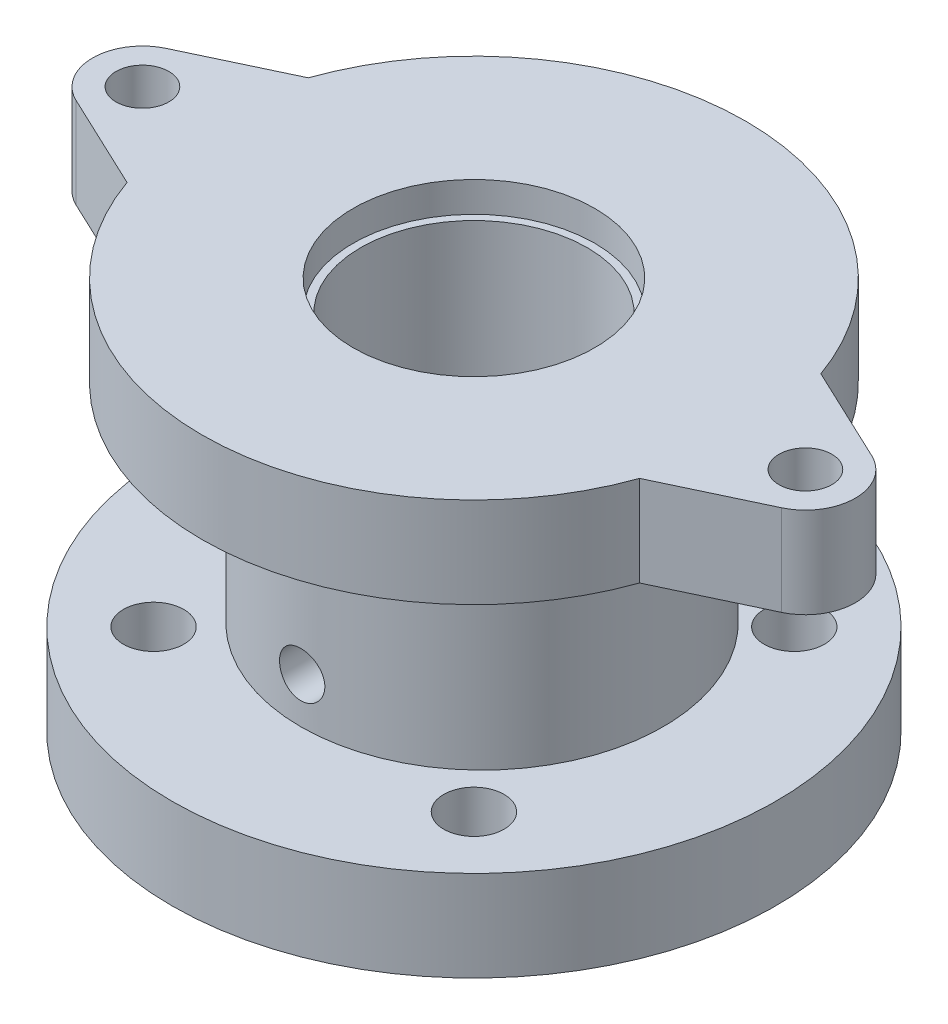
SolidWorks part; units mm, degrees
ref_plane "Front Plane" through (0, 0, 0) normal (0, 0, 1) x (1, 0, 0)
ref_plane "Top Plane" through (0, 0, 0) normal (0, 1, 0) x (1, 0, 0)
ref_plane "Right Plane" through (0, 0, 0) normal (1, 0, 0) x (0, 0, -1)
sketch "Sketch1" plane through (0, 0, 0) normal (0, 1, 0) x (1, 0, 0)
  circle A0 centre (0, 0) radius 7.5
  circle A1 centre (0, 0) radius 20
  dimension "D1" = 40
  dimension "D2" = 15
extrude "Boss-Extrude1" add sketch "Sketch1" along normal blind 6
sketch "Sketch2" plane through (0, 6, 0) normal (0, 1, 0) x (1, 0, 0)
  circle A0 centre (0, 0) radius 7.5
  circle A1 centre (0, 0.5354) radius 12
  dimension "D1" = 24
extrude "Boss-Extrude2" add sketch "Sketch2" along normal blind 14
sketch "Sketch3" plane through (0, 0, 0) normal (0, 0, 1) x (1, 0, 0)
  circle A0 centre (0, 9) radius 1.5
  dimension "D1" = 9
  dimension "D2" = 3
extrude "Cut-Extrude1" cut sketch "Sketch3" against normal through all both and the other way through all
sketch "Sketch4" plane through (0, 20, 0) normal (0, 1, 0) x (1, 0, 0)
  circle A0 centre (0, 0) radius 18
  circle A1 centre (0, 0) radius 7.5
  dimension "D1" = 36
extrude "Boss-Extrude3" add sketch "Sketch4" along normal blind 6
sketch "Sketch5" plane through (0, 26, 0) normal (0, 1, 0) x (1, 0, 0)
  line L0 (-21.95, 0) -> (21.95, 0) construction
  line L1 (-23.3588, 2.9842) -> (-16.9706, 6)
  line L2 (-23.3588, -2.9842) -> (-16.9706, -6)
  line L3 (23.3588, 2.9842) -> (16.9706, 6)
  line L4 (23.3588, -2.9842) -> (16.9706, -6)
  line L5 (-25.25, 0) -> (25.25, 0) construction
  circle A0 centre (-21.95, 0) radius 1.75
  circle A1 centre (21.95, 0) radius 1.75
  arc A2 (-23.3588, 2.9842) -> (-23.3588, -2.9842) centre (-21.95, 0) ccw
  arc A3 (23.3588, -2.9842) -> (23.3588, 2.9842) centre (21.95, 0) ccw
  arc A4 (-16.9706, 6) -> (-16.9706, -6) centre (0, 0) ccw
  arc A5 (16.9706, -6) -> (16.9706, 6) centre (0, 0) ccw
  circle A6 centre (0, 0) radius 18 construction
  point P3 (0, 0)
  point P14 (18, 0)
  point P15 (0, 0)
  point P16 (-18, 0)
  point P19 (0, 0)
  dimension "D2" = 3.5
  dimension "D3" = 3.5
  dimension "D1" = 43.9
  dimension "D4" = 12
  dimension "D5" = 50.5
extrude "Boss-Extrude4" add sketch "Sketch5" against normal up to surface (6 mm away) up to face at (0, 20, 11.4646)
sketch "Sketch6" plane through (0, 0, 0) normal (0, -1, 0) x (1, 0, 0)
  line L0 (0, 0) -> (-18.2577, 0) construction
  line L1 (0, 0) -> (-10.6066, 10.6066) construction
  circle A0 centre (-10.6066, 10.6066) radius 2
  circle A1 centre (10.6066, 10.6066) radius 2
  circle A2 centre (10.6066, -10.6066) radius 2
  circle A3 centre (-10.6066, -10.6066) radius 2
  point P14 (0, 0)
  dimension "D2" = 15
  dimension "D3" = 4
  dimension "D1" = 45
  dimension "D4" = 4
extrude "Cut-Extrude2" cut sketch "Sketch6" against normal up to surface (6 mm away) and the other way through all up to face at (0, 6, 20)
sketch "Sketch7" plane through (0, 26, 0) normal (0, 1, 0) x (1, 0, 0)
  circle A0 centre (0, 0) radius 8
  dimension "D1" = 16
extrude "Cut-Extrude3" cut sketch "Sketch7" against normal blind 2
